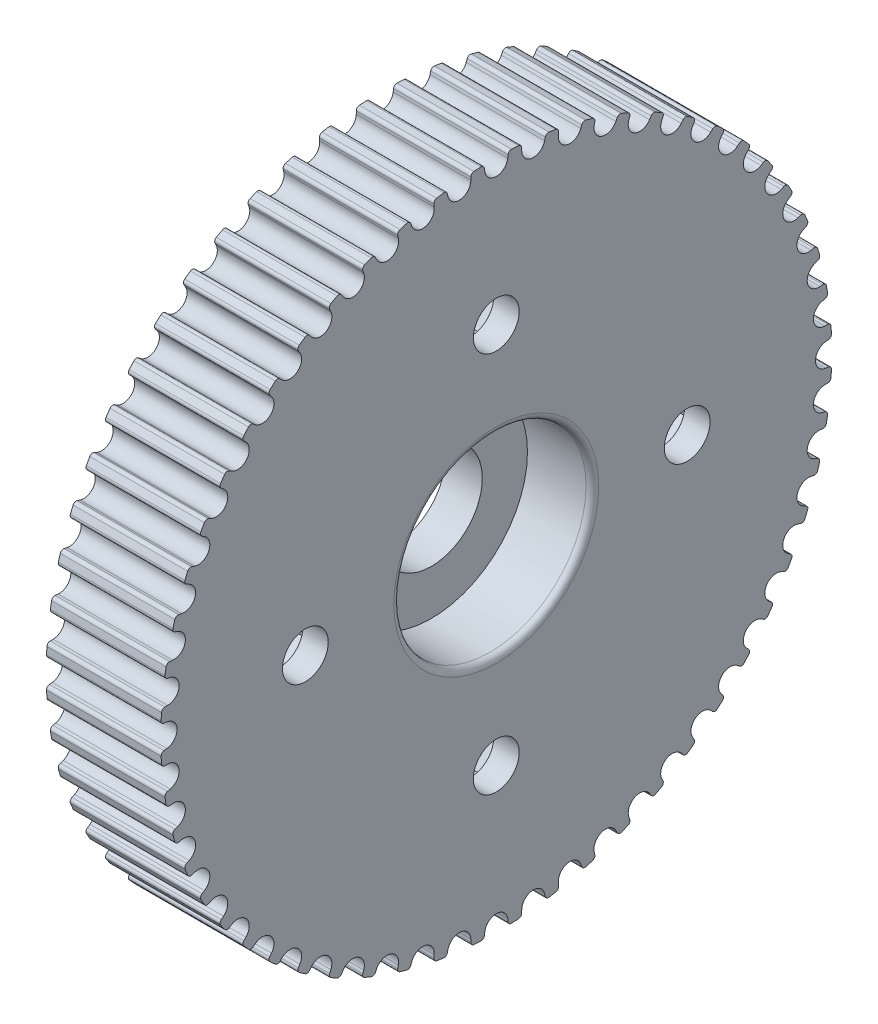
SolidWorks part; units mm, degrees
ref_plane "前视基准面" through (0, 0, 0) normal (0, 0, 1) x (1, 0, 0)
ref_plane "上视基准面" through (0, 0, 0) normal (0, 1, 0) x (1, 0, 0)
ref_plane "右视基准面" through (0, 0, 0) normal (1, 0, 0) x (0, 0, -1)
sketch "草图1" plane through (0, 0, 0) normal (0, 0, 1) x (1, 0, 0)
  line L0 (0, 0) -> (64.8368, 0) construction
  line L1 (0, 5.2718) -> (0, 26.359)
  line L2 (0, 26.359) -> (9, 26.359)
  line L3 (9, 26.359) -> (9, 10.5436)
  line L10 (9, 10.5436) -> (9, 0)
  line L11 (9, 0) -> (0, 0)
  line L12 (0, 0) -> (0, 5.2718)
  dimension "B" = 9
  dimension "da" = 52.718
revolve "旋转1" add sketch "草图1" angle 360 about L0
ref_axis "基准轴1" through (-0.45, 0, 0) along (1, 0, 0)
sketch "草图6" plane through (0, 0, 0) normal (1, 0, 0) x (0, 0, -1)
  line L0 (0, 0) -> (0, 30.6512) construction
  line L1 (0.9309, 26.1036) -> (0.9032, 25.8781)
  line L2 (1.4605, 26.3185) -> (1.6571, 27.9201)
  line L3 (-1.4605, 26.3185) -> (-1.6571, 27.9201)
  line L4 (-0.9309, 26.1036) -> (-0.9032, 25.8781)
  circle A0 centre (0, 0) radius 26.359 construction
  circle A1 centre (0, 0) radius 25.079 construction
  arc A2 (-0.9032, 25.8781) -> (0.9032, 25.8781) centre (0, 25.989) ccw
  arc A3 (1.6571, 27.9201) -> (-1.6571, 27.9201) centre (0, 0) ccw
  arc A4 (0.9309, 26.1036) -> (1.2008, 26.3316) centre (1.189, 26.0719) cw
  arc A5 (1.2008, 26.3316) -> (1.4605, 26.3185) centre (0, 0) cw
  arc A6 (-1.2008, 26.3316) -> (-1.4605, 26.3185) centre (0, 0) ccw
  arc A7 (-0.9309, 26.1036) -> (-1.2008, 26.3316) centre (-1.189, 26.0719) ccw
  point P7 (0, 1.9)
  point P8 (0, 29.3712)
  point P15 (0.9601, 26.3415)
  dimension "D1" = 50.158
  dimension "ra" = 0.26
  dimension "rf" = 0.91
  dimension "hg" = 1.28
  dimension "D3" = 0.26
  dimension "D4" = 1.6136
  dimension "angle" = 14
  dimension "bw" = 1.9
extrude "切除-拉伸2" cut sketch "草图6" along normal up to next
pattern_circular "阵列(圆周)3" count 56 over 360 about axis through (-0.45, 0, 0) along (1, 0, 0) of "切除-拉伸2"
sketch "草图7" plane through (0, 0, 0) normal (-1, 0, 0) x (0, 0, 1)
  circle A0 centre (0, 0) radius 21.25
  dimension "D1" = 42.5
extrude "切除-拉伸4" cut sketch "草图7" against normal blind 5
sketch "草图8" plane through (9, 0, 0) normal (1, 0, 0) x (0, 0, -1)
  circle A0 centre (0, 0) radius 4
  dimension "D1" = 8
chamfer "倒角1" distance 1 angle 45 1 edges at (0, 0, 21.25)
sketch "草图10" plane through (9, 0, 0) normal (1, 0, 0) x (0, 0, -1)
  circle A0 centre (0, 0) radius 4
  dimension "D1" = 8
sketch "草图11" plane through (5, 0, 0) normal (-1, 0, 0) x (0, 0, 1)
  circle A0 centre (0, 0) radius 12.5
  dimension "D1" = 25
extrude "凸台-拉伸2" add sketch "草图11" along normal blind 4
sketch "草图12" plane through (9, 0, 0) normal (1, 0, 0) x (0, 0, -1)
  circle A0 centre (0, 0) radius 4
  dimension "D1" = 8
extrude "切除-拉伸8" cut sketch "草图12" against normal blind 32
chamfer "倒角3" distance 1 angle 45 1 edges at (1, 0, 12.5)
sketch "草图13" plane through (9, 0, 0) normal (1, 0, 0) x (0, 0, -1)
  circle A0 centre (0, 0) radius 15 construction
  circle A1 centre (0, 15) radius 1.8
  circle A2 centre (15, 0) radius 1.8
  circle A3 centre (0, -15) radius 1.8
  circle A4 centre (-15, 0) radius 1.8
  point P14 (0, 0)
  dimension "D1" = 30
  dimension "D2" = 3.6
  dimension "D3" = 4
extrude "切除-拉伸9" cut sketch "草图13" against normal blind 50
sketch "草图14" plane through (5, 0, 0) normal (-1, 0, 0) x (0, 0, 1)
  line L0 (3.2909, 15) -> (1.6454, 17.85)
  line L1 (-15, 3.2909) -> (-17.85, 1.6454)
  line L2 (-17.85, 1.6454) -> (-17.85, -1.6454)
  line L3 (-17.85, -1.6454) -> (-15, -3.2909)
  line L4 (-15, -3.2909) -> (-12.15, -1.6454)
  line L5 (-12.15, -1.6454) -> (-12.15, 1.6454)
  line L6 (-12.15, 1.6454) -> (-15, 3.2909)
  line L7 (1.6454, 17.85) -> (-1.6454, 17.85)
  line L8 (-1.6454, 17.85) -> (-3.2909, 15)
  line L9 (-3.2909, 15) -> (-1.6454, 12.15)
  line L10 (-1.6454, 12.15) -> (1.6454, 12.15)
  line L11 (1.6454, 12.15) -> (3.2909, 15)
  line L12 (15, -3.2909) -> (17.85, -1.6454)
  line L13 (17.85, -1.6454) -> (17.85, 1.6454)
  line L14 (17.85, 1.6454) -> (15, 3.2909)
  line L15 (15, 3.2909) -> (12.15, 1.6454)
  line L16 (12.15, 1.6454) -> (12.15, -1.6454)
  line L17 (12.15, -1.6454) -> (15, -3.2909)
  line L18 (-3.2909, -15) -> (-1.6454, -17.85)
  line L19 (-1.6454, -17.85) -> (1.6454, -17.85)
  line L20 (1.6454, -17.85) -> (3.2909, -15)
  line L21 (3.2909, -15) -> (1.6454, -12.15)
  line L22 (1.6454, -12.15) -> (-1.6454, -12.15)
  line L23 (-1.6454, -12.15) -> (-3.2909, -15)
  circle A0 centre (-15, 0) radius 2.85 construction
  point P30 (0, 0)
  dimension "D1" = 5.7
  dimension "D2" = 4
extrude "切除-拉伸11" cut sketch "草图14" against normal blind 2 and the other way blind 8
sketch "草图15" plane through (9, 0, 0) normal (1, 0, 0) x (0, 0, -1)
  circle A0 centre (0, 0) radius 7.55
  dimension "D1" = 15.1
extrude "切除-拉伸12" cut sketch "草图15" against normal blind 5.1
fillet "圆角1" radius 0.5 1 edges at (9, 0, -7.55)
equation "\"D1@草图6\" = \"da@草图1\"  - \"hg@草图6\" - \"hg@草图6\""
equation "\"D3@草图6\" = \"ra@草图6\""
